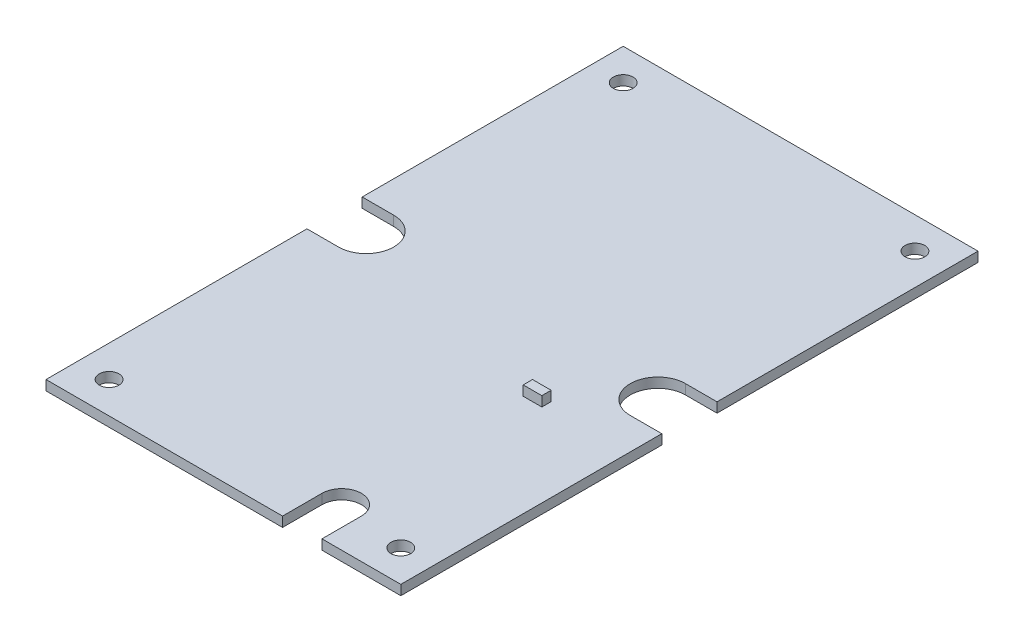
SolidWorks part; units mm, degrees
ref_plane "Front Plane" through (0, 0, 0) normal (0, 0, 1) x (1, 0, 0)
ref_plane "Top Plane" through (0, 0, 0) normal (0, 1, 0) x (1, 0, 0)
ref_plane "Right Plane" through (0, 0, 0) normal (1, 0, 0) x (0, 0, -1)
sketch "Sketch1" plane through (0, 0, 0) normal (0, 1, 0) x (1, 0, 0)
  line L1 (0, 0) -> (57.15, 0)
  line L2 (0, 0) -> (0, 92.964)
  line L3 (0, 92.964) -> (57.15, 92.964)
  line L4 (57.15, 0) -> (57.15, 92.964)
  dimension "D1" = 57.15
  dimension "D2" = 92.964
extrude "Boss-Extrude1" add sketch "Sketch1" along normal blind 1.5875
sketch "Sketch2" plane through (0, 1.5875, 0) normal (0, 1, 0) x (1, 0, 0)
  line L0 (5.08, 46.482) -> (0, 46.482) construction
  line L1 (5.08, 5.08) -> (52.07, 5.08) construction
  line L2 (5.08, 5.08) -> (5.08, 87.884) construction
  line L3 (5.08, 87.884) -> (52.07, 87.884) construction
  line L4 (52.07, 5.08) -> (52.07, 87.884) construction
  line L5 (0, 92.964) -> (0, 0) construction
  line L6 (52.07, 46.482) -> (57.15, 46.482) construction
  line L7 (57.15, 0) -> (57.15, 92.964) construction
  line L8 (28.575, 87.884) -> (28.575, 92.964) construction
  line L9 (57.15, 92.964) -> (0, 92.964) construction
  line L10 (28.575, 5.08) -> (28.575, 0) construction
  line L11 (0, 0) -> (57.15, 0) construction
  circle A0 centre (5.08, 87.884) radius 1.5875
  circle A1 centre (52.07, 87.884) radius 1.5875
  circle A2 centre (5.08, 5.08) radius 1.5875
  circle A3 centre (52.07, 5.08) radius 1.5875
  dimension "D3" = 3.175
  dimension "D1" = 46.99
  dimension "D2" = 82.804
extrude "Cut-Extrude1" cut sketch "Sketch2" against normal through all contours A0 | A1 | A2 | A3
sketch "Sketch3" plane through (0, 1.5875, 0) normal (0, 1, 0) x (1, 0, 0)
  line L2 (57.15, 92.964) -> (0, 92.964) construction
  line L3 (57.15, 0) -> (57.15, 92.964) construction
  line L4 (52.07, 42.037) -> (57.15, 42.037)
  line L5 (57.15, 42.037) -> (57.15, 50.927)
  line L6 (57.15, 50.927) -> (52.07, 50.927)
  line L7 (28.575, 0) -> (28.575, 92.964) construction
  line L8 (0, 0) -> (57.15, 0) construction
  line L9 (0, 50.927) -> (5.08, 50.927)
  line L10 (0, 42.037) -> (0, 50.927)
  line L11 (5.08, 42.037) -> (0, 42.037)
  line L12 (57.15, 46.482) -> (0, 46.482) construction
  circle A1 centre (52.07, 46.482) radius 4.445
  circle A2 centre (5.08, 46.482) radius 4.445
  line M5 (0, 92.964) -> (0, 0)
  line M7 (57.15, 0) -> (57.15, 92.964)
  dimension "D3" = 8.89
  dimension "D2" = 5.08
extrude "Cut-Extrude2" cut sketch "Sketch3" against normal through all contours A1 L4 L6 M7 | A1 | A2 | L11 A2 L9 M5 region at (55.2855, 1.5875, -43.2665) region at (52.07, 1.5875, -46.482) region at (2.54, 1.5875, -50.8246) region at (5.08, 1.5875, -46.482)
sketch "Sketch4" plane through (0, 1.5875, 0) normal (0, 1, 0) x (1, 0, 0)
  line L0 (0, 0) -> (57.15, 0) construction
  line L1 (44.45, 6.35) -> (44.45, 0)
  line L2 (44.45, 0) -> (38.1, 0)
  line L3 (38.1, 0) -> (38.1, 6.35)
  line L4 (41.275, 92.964) -> (41.275, 0) construction
  line L7 (57.15, 0) -> (57.15, 42.037) construction
  circle A0 centre (41.275, 6.35) radius 3.175
  line M15 (0, 0) -> (57.15, 0)
  dimension "D1" = 6.35
  dimension "D2" = 6.35
  dimension "D3" = 15.875
extrude "Cut-Extrude3" cut sketch "Sketch4" against normal up to next contours A0 L4 | L4 A0 | L4 A0 L3 M15 | A0 L4 L2 L1 region at (42.6225, 1.5875, -6.35) region at (43.0177, 1.5875, -1.9933) region at (39.9275, 1.5875, -6.35) region at (39.5323, 1.5875, -1.9933)
sketch "Sketch5" plane through (0, 0, 0) normal (0, -1, 0) x (1, 0, 0)
  line L1 (3.0647, -59.9873) -> (7.0647, -59.9873)
  line L2 (3.0647, -59.9873) -> (3.0647, -55.9873)
  line L3 (3.0647, -55.9873) -> (7.0647, -55.9873)
  line L4 (7.0647, -59.9873) -> (7.0647, -55.9873)
  line L5 (3.1648, -78.6771) -> (7.1648, -78.6771)
  line L6 (3.1648, -78.6771) -> (3.1648, -81.6771)
  line L7 (3.1648, -81.6771) -> (7.1648, -81.6771)
  line L8 (7.1648, -78.6771) -> (7.1648, -81.6771)
  circle A1 centre (5.08, -70.739) radius 4.7244
  point P6 (3.1565, -81.7455)
  point P7 (3.1648, -81.6771)
  dimension "D1" = 9.4488
  dimension "D2" = 4
  dimension "D3" = 4
  dimension "D4" = 3
  dimension "D5" = 4
extrude "Boss-Extrude2" add sketch "Sketch5" along normal blind 6.35 contours A1 region at (5.08, 0, -70.739)
extrude "Boss-Extrude3" add sketch "Sketch5<3>" along normal blind 1.5875 contours L1 L4 L3 L2 | L8 L5 L6 L7 region at (5.0647, 0, -57.9873) region at (5.1648, 0, -80.1771)
sketch "Sketch5<3>" plane through (0, 0, 0) normal (0, -1, 0) x (1, 0, 0) same geometry as "Sketch5"
sketch "Sketch7" plane through (0, 1.5875, 0) normal (0, 1, 0) x (1, 0, 0)
  line L0 (57.15, 92.964) -> (0, 92.964) construction
  line L1 (43.7705, 36.092) -> (40.7705, 36.092)
  line L2 (43.7705, 36.092) -> (43.7705, 37.592)
  line L3 (43.7705, 37.592) -> (40.7705, 37.592)
  line L4 (40.7705, 36.092) -> (40.7705, 37.592)
  dimension "D1" = 3
  dimension "D2" = 1.5
  dimension "D3" = 55.372
extrude "Boss-Extrude4" add sketch "Sketch7" along normal blind 1.5875
